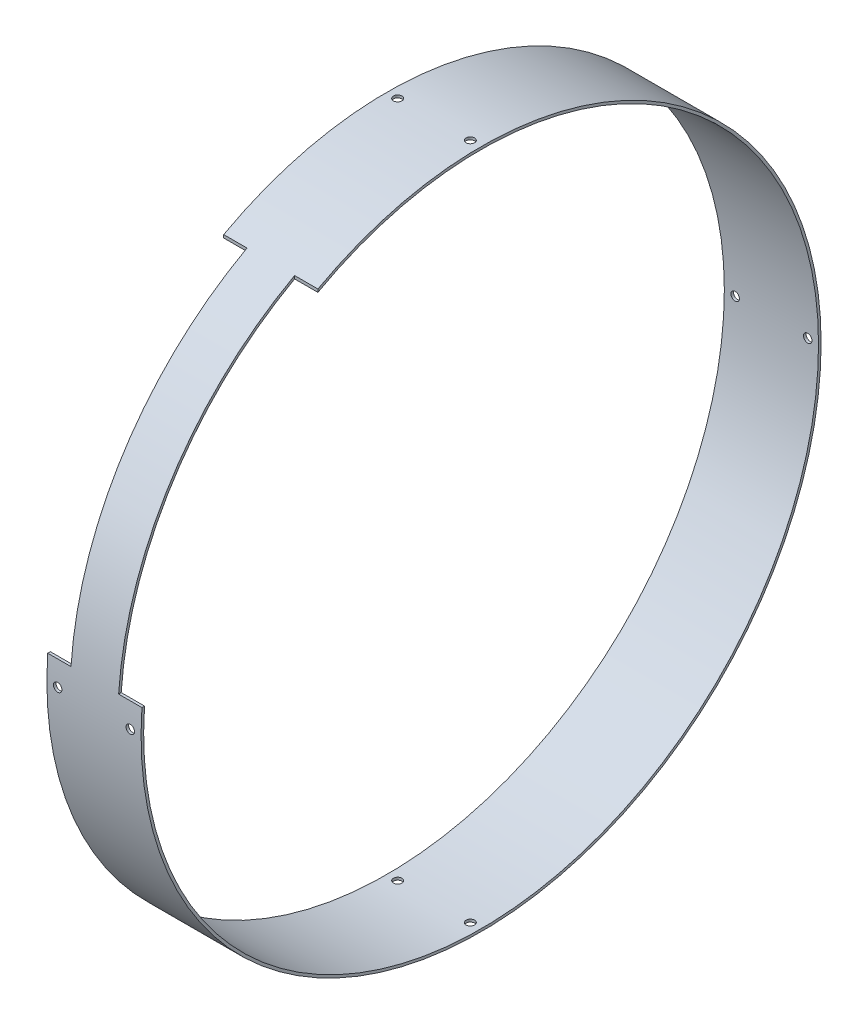
SolidWorks part; units mm, degrees
material "6061 Alloy"
ref_plane "Front Plane" through (0, 0, 0) normal (0, 0, 1) x (1, 0, 0)
ref_plane "Top Plane" through (0, 0, 0) normal (0, 1, 0) x (1, 0, 0)
ref_plane "Right Plane" through (0, 0, 0) normal (1, 0, 0) x (0, 0, -1)
sketch "Sketch1" plane through (0, 0, 0) normal (1, 0, 0) x (0, 0, -1)
  circle A0 centre (0, 0) radius 100
  circle A1 centre (0, 0) radius 99.238
  dimension "D1" = 200
  dimension "D2" = 0.762
extrude "Boss-Extrude1" add sketch "Sketch1" along normal blind 27.7
ref_plane "Plane1" through (0, 0, 100) normal (0, 0, 1) x (1, 0, 0)
hole_wizard "Ø2.5mm Dowel Hole1" positions "Sketch2" profile "Sketch3" hole size "Ø2.5" standard "ANSI Metric" end condition through all
sketch "Sketch2" plane through (0, 0, 100) normal (0, 0, 1) x (1, 0, 0)
  line L0 (27.7, -100) -> (27.7, 100) construction
  line L1 (0, 100) -> (0, -100) construction
  point P0 (24.525, 0)
  point P2 (3.175, 0)
  dimension "D1" = 3.175
  dimension "D2" = 3.175
sketch "Sketch3" plane through (24.525, 0, 100) normal (1, 0, 0) x (0, -1, 0)
  line L0 (0, 0) -> (0, 200)
  line L1 (0, 200) -> (1.25, 200)
  line L2 (1.25, 200) -> (1.25, 0)
  line L5 (1.25, 0) -> (0, 0)
  line L11 (0, -6.35) -> (0, 107.95) construction
  dimension "Thru Hole Dia." = 2.5
  dimension "Thru Hole Depth" = 200
ref_plane "Plane2" through (0, 100, 0) normal (0, 1, 0) x (1, 0, 0)
hole_wizard "Ø2.5mm Dowel Hole2" positions "Sketch4" profile "Sketch5" hole size "Ø2.5" standard "ANSI Metric" end condition through all
sketch "Sketch4" plane through (0, 100, 0) normal (0, 1, 0) x (1, 0, 0)
  line L0 (27.7, -100) -> (27.7, 100) construction
  line L1 (0, 100) -> (0, -100) construction
  point P0 (24.525, 0)
  point P2 (3.175, 0)
  dimension "D1" = 3.175
  dimension "D2" = 3.175
sketch "Sketch5" plane through (24.525, 100, 0) normal (1, 0, 0) x (0, 0, 1)
  line L0 (0, 0) -> (0, 200)
  line L1 (0, 200) -> (1.25, 200)
  line L2 (1.25, 200) -> (1.25, 0)
  line L5 (1.25, 0) -> (0, 0)
  line L11 (0, -6.35) -> (0, 107.95) construction
  dimension "Thru Hole Dia." = 2.5
  dimension "Thru Hole Depth" = 200
ref_plane "Plane3" through (0, 0, 0) normal (0, 0.7071, -0.7071) x (-1, 0, 0)
ref_plane "Plane4" through (0, 0, 0) normal (0, 0.7071, 0.7071) x (-1, 0, 0)
sketch "Sketch7" plane through (0, 0, 0) normal (0, 0.7071, 0.7071) x (-1, 0, 0)
  line L0 (-27.7, 7.5) -> (-27.7, -7.5) construction
  line L1 (-27.7, 7.5) -> (-21.35, 7.5) construction
  line L2 (-27.7, -7.5) -> (-21.35, -7.5) construction
  line L3 (-21.35, 7.5) -> (-21.35, -7.5) construction
  line L4 (-27.7, 100) -> (-27.7, -100) construction
  line L5 (-28.2, 8) -> (-20.85, 8)
  line L6 (-20.85, 8) -> (-20.85, -8)
  line L7 (-28.2, -8) -> (-20.85, -8)
  line L8 (-28.2, 8) -> (-28.2, -8)
  point P6 (-21.35, 0)
  dimension "D1" = 6.35
  dimension "D2" = 15
  dimension "D3" = 0.5
extrude "Cut-Extrude2" [suppressed] cut sketch "Sketch7" against normal through all both and the other way through all
sketch "Sketch8" plane through (0, 100, 0) normal (0, 1, 0) x (1, 0, 0)
  line L1 (27.85, -48) -> (20.85, -48)
  line L2 (27.85, -48) -> (27.85, -100)
  line L3 (27.85, -100) -> (20.85, -100)
  line L4 (20.85, -48) -> (20.85, -100)
  line L5 (4.425, -100) -> (23.2751, -100) construction
  line L7 (13.85, -1100) -> (13.85, 48900) construction
  line L8 (-0.15, -100) -> (6.85, -100)
  line L9 (6.85, -48) -> (6.85, -100)
  line L10 (-0.15, -48) -> (6.85, -48)
  line L11 (-0.15, -48) -> (-0.15, -100)
  point P14 (13.85, -100)
  point P16 (0, 0)
  point P17 (0, 0)
  dimension "D1" = 7
  dimension "D2" = 52
  dimension "D3" = 7
extrude "Cut-Extrude3" cut sketch "Sketch8" against normal offset from surface (93 mm away) 7 up to plane "Top Plane"
